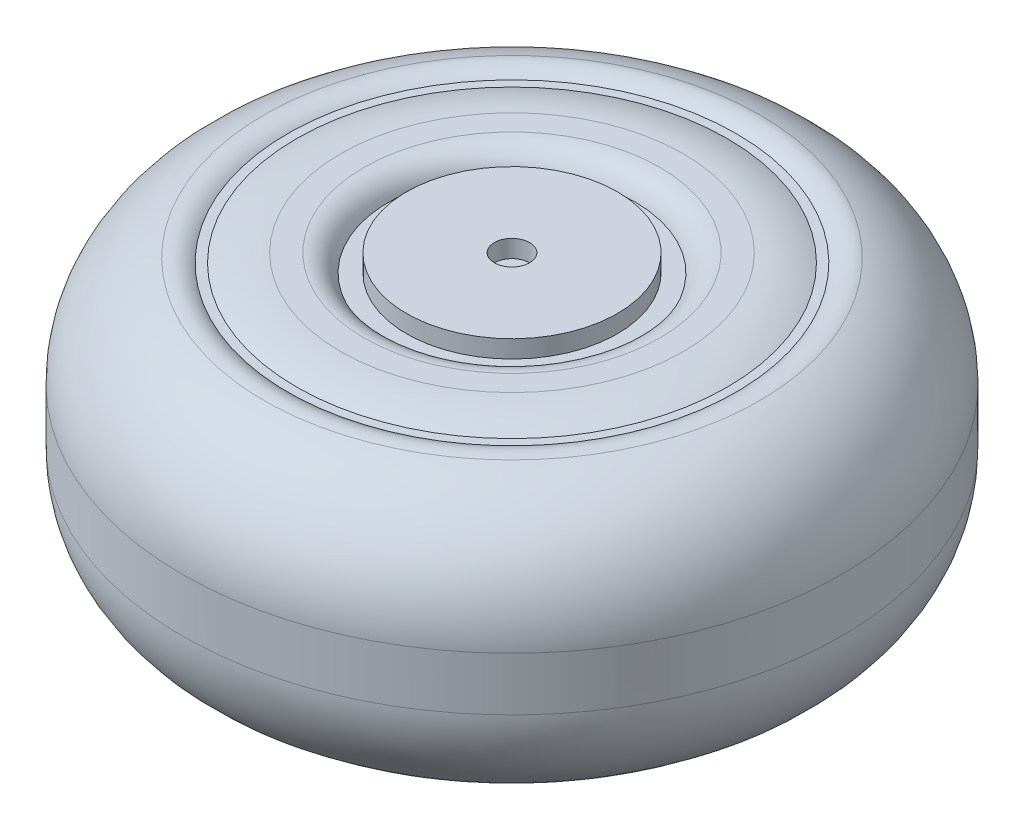
SolidWorks part; units mm, degrees
ref_plane "前视基准面" through (0, 0, 0) normal (0, 0, 1) x (1, 0, 0)
ref_plane "上视基准面" through (0, 0, 0) normal (0, 1, 0) x (1, 0, 0)
ref_plane "右视基准面" through (0, 0, 0) normal (1, 0, 0) x (0, 0, -1)
sketch "草图1" plane through (0, 0, 0) normal (1, 0, 0) x (0, 0, -1)
  line L0 (25.5, 32) -> (35.5, 32)
  line L1 (0, 0) -> (37.5, 0) construction
  line L2 (0, 0) -> (0, 32)
  line L3 (0, 32) -> (12, 32)
  line L4 (37.5, 2) -> (37.5, 30)
  line L5 (13, 32) -> (23.5, 32)
  line L6 (0, 16) -> (37.5, 16) construction
  line L7 (37.5, 30) -> (35.5, 30)
  line L8 (35.5, 32) -> (35.5, 30)
  line L9 (12, 32) -> (12, 31)
  line L10 (23.5, 32) -> (23.5, 30)
  line L11 (23.5, 30) -> (25.5, 30)
  line L12 (25.5, 32) -> (25.5, 30)
  line L13 (12, 31) -> (13, 31)
  line L14 (13, 32) -> (13, 31)
  line L15 (13, 0) -> (13, 1)
  line L16 (12, 1) -> (13, 1)
  line L17 (25.5, 0) -> (25.5, 2)
  line L18 (23.5, 2) -> (25.5, 2)
  line L19 (23.5, 0) -> (23.5, 2)
  line L20 (12, 0) -> (12, 1)
  line L21 (35.5, 0) -> (35.5, 2)
  line L22 (37.5, 2) -> (35.5, 2)
  line L23 (13, 0) -> (23.5, 0)
  line L24 (0, 0) -> (12, 0)
  line L25 (25.5, 0) -> (35.5, 0)
  point P12 (35.5, 31)
  dimension "D1" = 37.5
  dimension "D2" = 32
  dimension "D3" = 2
  dimension "D4" = 2
  dimension "D5" = 2
  dimension "D6" = 10
  dimension "D7" = 2
  dimension "D8" = 1
  dimension "D9" = 12
  dimension "D10" = 1
revolve "旋转1" add sketch "草图1" angle 360 about L4
fillet "圆角1" radius 13 2 edges at (0, 32, -75) (0, 0, -75)
fillet "圆角2" radius 13 2 edges at (0, 32, -62) (0, 0, -62)
fillet "圆角3" radius 3 1 edges at (0, 32, -51.5)
fillet "圆角4" radius 3 1 edges at (0, 32, -63)
